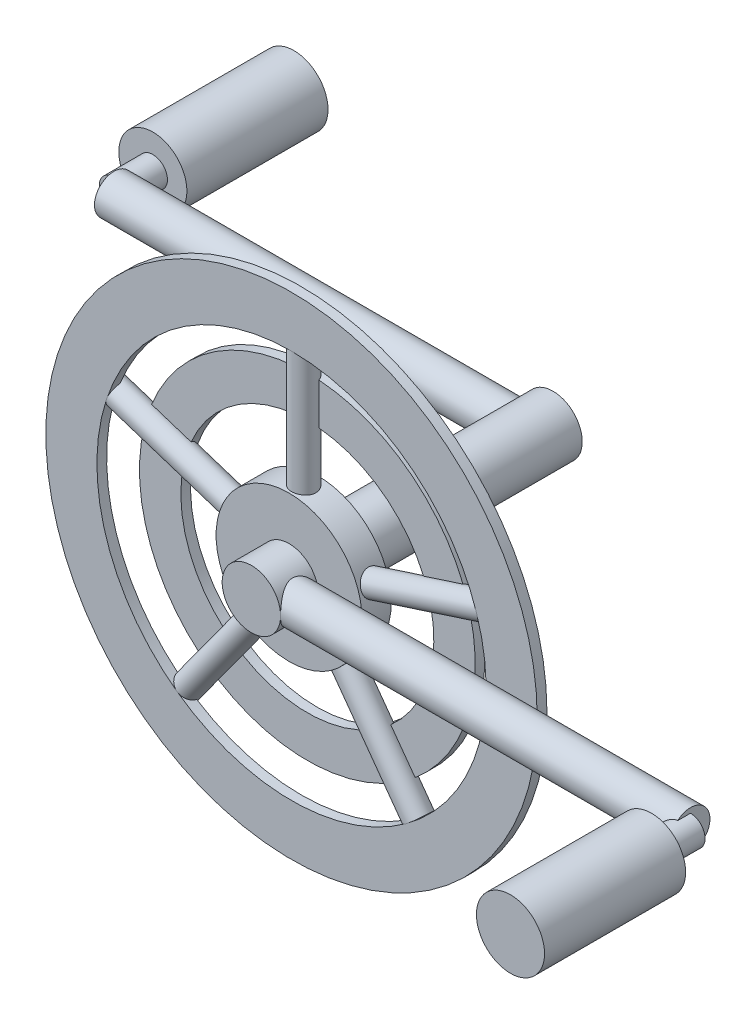
SolidWorks part; units mm, degrees
ref_plane "Alzado" through (0, 0, 0) normal (0, 0, 1) x (1, 0, 0)
ref_plane "Planta" through (0, 0, 0) normal (0, 1, 0) x (1, 0, 0)
ref_plane "Vista lateral" through (0, 0, 0) normal (1, 0, 0) x (0, 0, -1)
sketch3d "Sk_Eje_pedalier"
  line L0 (0, 0, -62) -> (0, 0, 62)
sweep "Eje_pedalier" add path "Sk_Eje_pedalier" circular profile diameter 24 parameters "D3"=24
sketch3d "Sk_Arana_centro"
  line L0 (0, 0, 34.5) -> (0, 0, 46.5)
sweep "Arana_centro" add path "Sk_Arana_centro" circular profile diameter 60 parameters "D3"=60
sketch3d "Sk_Brazo_arana"
  line L0 (0, 0, 40.5) -> (0, 90, 40.5)
  dimension "D1" = 90
sweep "Brazo_arana" add path "Sk_Brazo_arana" circular profile diameter 10 parameters "D3"=10
ref_axis "Eje_bielas" through (0, 0, -62) along (0, 0, 1)
pattern_circular "Matriz_brazos" count 5 over 360 about axis through (0, 0, -62) along (0, 0, 1) of "Brazo_arana"
sketch "Sk_Plato_grande" plane through (0, 0, 0) normal (0, 0, 1) x (1, 0, 0)
  circle A0 centre (0, 0) radius 101
  circle A1 centre (0, 0) radius 80
  dimension "D1" = 202
  dimension "D2" = 160
extrude "Plato_grande" add sketch "Sk_Plato_grande" along normal blind 4 from offset 41.5
sketch "Sk_Plato_pequeno" plane through (0, 0, 0) normal (0, 0, 1) x (1, 0, 0)
  circle A0 centre (0, 0) radius 69
  circle A1 centre (0, 0) radius 52
  dimension "D1" = 138
  dimension "D2" = 104
extrude "Plato_pequeno" add sketch "Sk_Plato_pequeno" along normal blind 4 from offset 35
sketch3d "Sk_Biela_dcha"
  line L0 (0, 0, 54) -> (172.5, 0, 54)
  dimension "D1" = 172.5
sweep "Biela_dcha" add path "Sk_Biela_dcha" circular profile diameter 16 parameters "D3"=16
sketch3d "Sk_Biela_izq"
  line L0 (0, 0, -54) -> (-172.5, 0, -54)
  dimension "D1" = 172.5
sweep "Biela_izq" add path "Sk_Biela_izq" circular profile diameter 16 parameters "D3"=16
sketch3d "Sk_Eje_pedal_dcho"
  line L0 (172.5, 0, 54) -> (172.5, 0, 75)
sweep "Eje_pedal_dcho" add path "Sk_Eje_pedal_dcho" circular profile diameter 12 parameters "D3"=12
sketch3d "Sk_Eje_pedal_izq"
  line L0 (-172.5, 0, -54) -> (-172.5, 0, -75)
sweep "Eje_pedal_izq" add path "Sk_Eje_pedal_izq" circular profile diameter 12 parameters "D3"=12
sketch3d "Sk_Pedal_dcho"
  line L0 (172.5, 0, 70) -> (172.5, 0, 128)
sweep "Pedal_dcho" add path "Sk_Pedal_dcho" circular profile diameter 28 parameters "D3"=28
sketch3d "Sk_Pedal_izq"
  line L0 (-172.5, 0, -128) -> (-172.5, 0, -70)
sweep "Pedal_izq" add path "Sk_Pedal_izq" circular profile diameter 28 parameters "D3"=28
